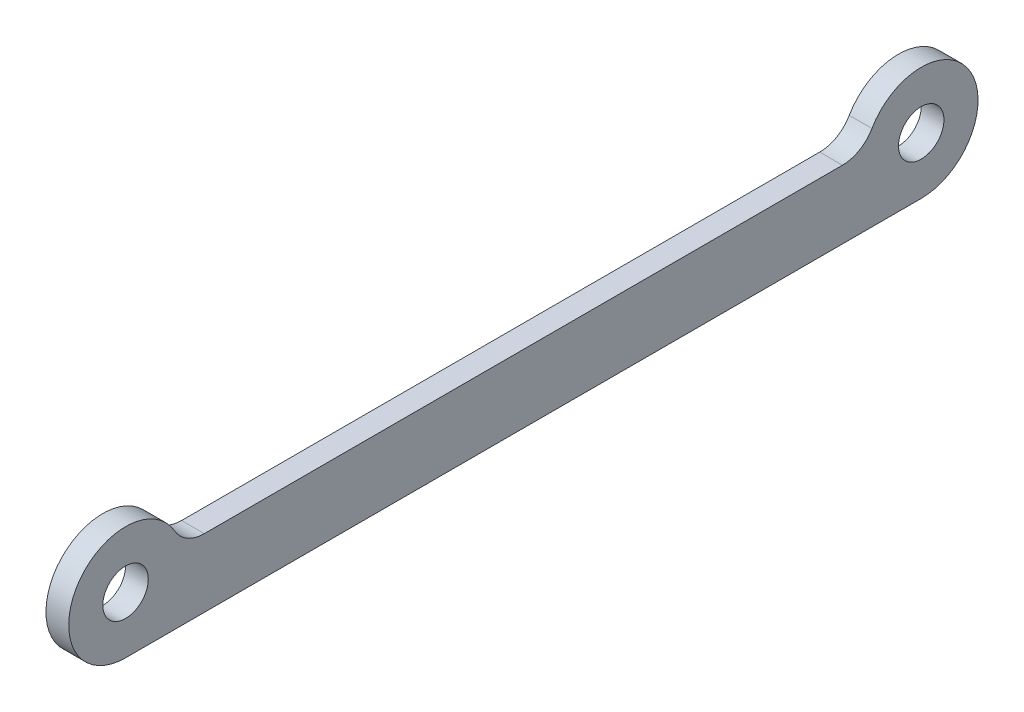
SolidWorks part; units mm, degrees
ref_plane "前视基准面" through (0, 0, 0) normal (0, 0, 1) x (1, 0, 0)
ref_plane "上视基准面" through (0, 0, 0) normal (0, 1, 0) x (1, 0, 0)
ref_plane "右视基准面" through (0, 0, 0) normal (1, 0, 0) x (0, 0, -1)
other "Configuration Table"
sketch "草图1" plane through (0, 0, 0) normal (1, 0, 0) x (0, 0, -1)
  line L1 (0, 0) -> (70, 0)
  line L2 (0, 0) -> (0, -6)
  line L3 (0, -6) -> (70, -6)
  line L4 (70, 0) -> (70, -6)
  circle A0 centre (70, -1) radius 5
  circle A1 centre (0, -1) radius 5
  circle A2 centre (70, -1) radius 2
  circle A3 centre (0, -1) radius 2
  point P12 (0, 0)
  point P14 (0, 0)
  point P15 (0, 0)
  dimension "D1" = 4
  dimension "D4" = 10
  dimension "D5" = 10
  dimension "D2" = 70
  dimension "D3" = 6
extrude "凸台-拉伸1" add sketch "草图1" along normal blind 2 contours L1 L4 L3 L2 | A1 | A0
extrude "切除-拉伸1" cut sketch "草图1<3>" along normal through all contours A3 | A2
sketch "草图1<3>" plane through (0, 0, 0) normal (1, 0, 0) x (0, 0, -1) same geometry as "草图1"
fillet "圆角1" radius 3 2 edges at (1, 0, -65.101) (1, 0, -4.899)
